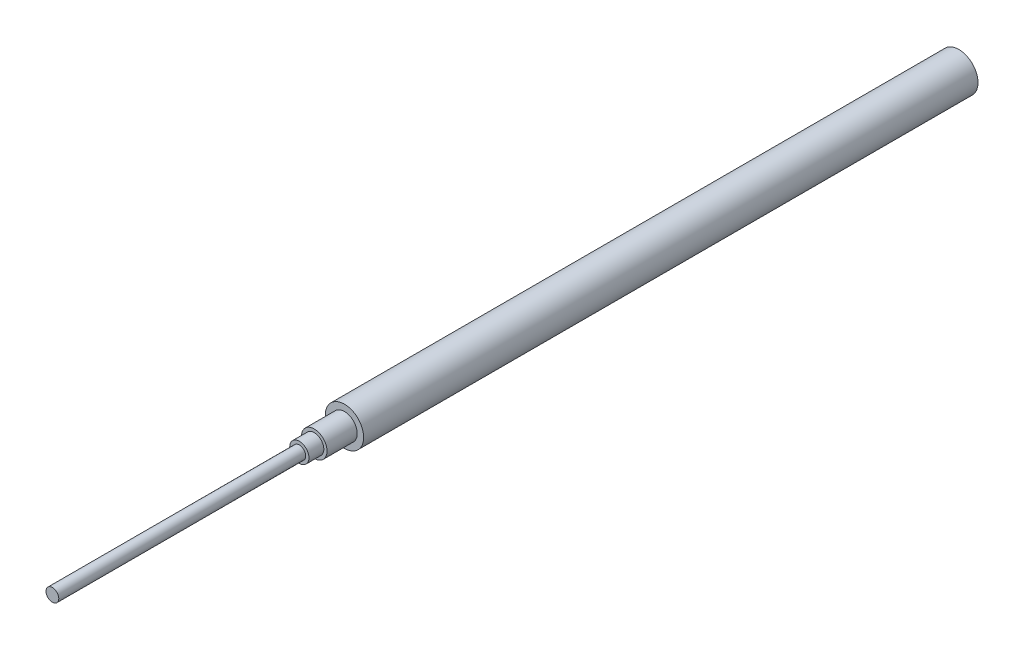
SolidWorks part; units mm, degrees
material "Plain Carbon Steel"
ref_plane "Front Plane" through (0, 0, 0) normal (0, 0, 1) x (1, 0, 0)
ref_plane "Top Plane" through (0, 0, 0) normal (0, 1, 0) x (1, 0, 0)
ref_plane "Right Plane" through (0, 0, 0) normal (1, 0, 0) x (0, 0, -1)
sketch "Sketch1" plane through (0, 0, 0) normal (0, 0, 1) x (1, 0, 0)
  circle A0 centre (0, 0) radius 4.7625
  dimension "D1" = 9.525
extrude "Boss-Extrude1" add sketch "Sketch1" along normal blind 152.5
sketch "Sketch2" plane through (0, 0, 0) normal (0, 0, 1) x (1, 0, 0)
  circle A0 centre (0, 0) radius 3.175
  dimension "D1" = 6.35
extrude "Boss-Extrude2" add sketch "Sketch2" along normal blind 160
sketch "Sketch3" plane through (0, 0, 0) normal (0, 0, 1) x (1, 0, 0)
  circle A0 centre (0, 0) radius 2.3812
  dimension "D1" = 4.7625
extrude "Boss-Extrude3" add sketch "Sketch3" along normal blind 163.7
sketch "Sketch4" plane through (0, 0, 0) normal (0, 0, 1) x (1, 0, 0)
  circle A0 centre (0, 0) radius 1.5875
  dimension "D1" = 3.175
extrude "Boss-Extrude4" add sketch "Sketch4" along normal blind 225
